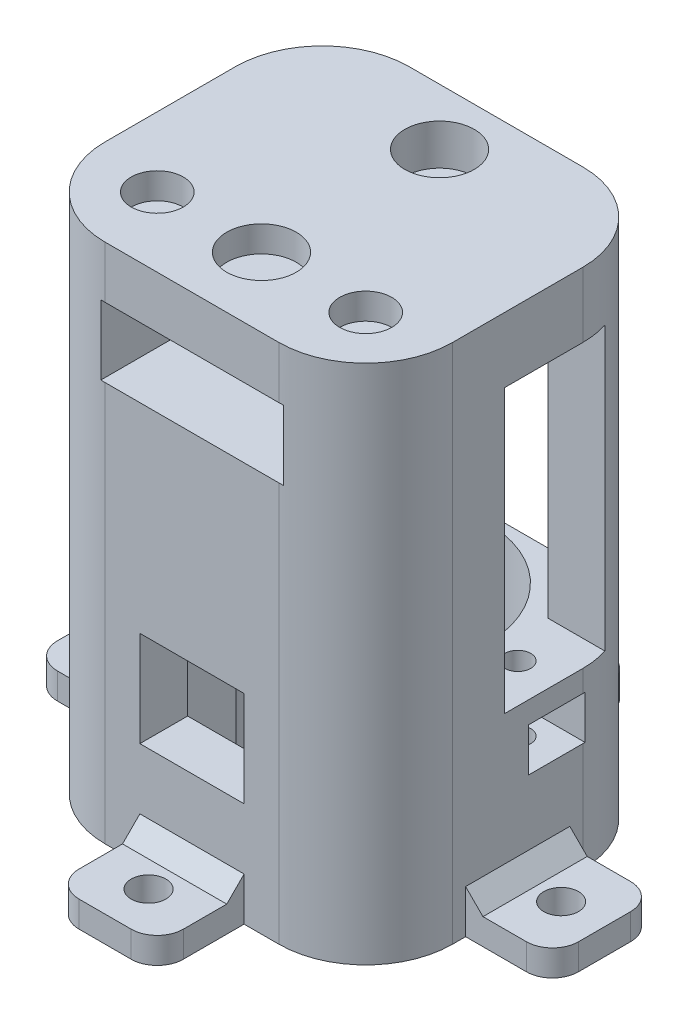
SolidWorks part; units mm, degrees
ref_plane "Plano frontal" through (0, 0, 0) normal (0, 0, 1) x (1, 0, 0)
ref_plane "Plano superior" through (0, 0, 0) normal (0, 1, 0) x (1, 0, 0)
ref_plane "Plano direito" through (0, 0, 0) normal (1, 0, 0) x (0, 0, -1)
sketch "Esboço2" plane through (0, 0, 0) normal (0, 1, 0) x (1, 0, 0)
  line L1 (0, 0) -> (40, 0)
  line L2 (0, 0) -> (0, 35)
  line L3 (0, 35) -> (40, 35)
  line L4 (40, 0) -> (40, 35)
  dimension "D1" = 40
  dimension "D2" = 35
extrude "Base" add sketch "Esboço2" along normal blind 20
sketch "Esboço3" plane through (0, 20, 0) normal (0, 1, 0) x (1, 0, 0)
  line L0 (20, -2.1425) -> (20, 46.202) construction
  line L1 (-2.8555, 22) -> (47.4642, 22) construction
  line L2 (40, 0) -> (40, 35) construction
  line L3 (40, 35) -> (0, 35) construction
  line L5 (11.25, 5.5) -> (28.75, 5.5)
  line L6 (11.25, 5.5) -> (11.25, 14.5)
  line L7 (11.25, 14.5) -> (28.75, 14.5)
  line L8 (28.75, 5.5) -> (28.75, 14.5)
  line L9 (11.25, 5.5) -> (28.75, 14.5) construction
  line L10 (11.25, 14.5) -> (28.75, 5.5) construction
  circle A0 centre (20, 22) radius 12
  point P10 (20, 10)
  dimension "D1" = 24
  dimension "D2" = 20
  dimension "D3" = 13
  dimension "D4" = 17.5
  dimension "D5" = 9
  dimension "D6" = 16.5
extrude "Furo do encaixe do motor" cut sketch "Esboço3" against normal through all contours A0 L7 L6 L5 L8 | L7 A0 | L7 A0 region at (20, 20, -8.4409) region at (20, 20, -23.3816) region at (20, 20, -12.6552)
sketch "Esboço5" plane through (0, 20, 0) normal (0, 1, 0) x (1, 0, 0)
  line L0 (41.6655, 22) -> (-3.8205, 22) construction
  line L1 (20, 37.517) -> (20, 6.483) construction
  circle A0 centre (4.5, 22) radius 1.5
  circle A1 centre (35.5, 22) radius 1.5
  point P10 (20, 22)
  dimension "D1" = 3
  dimension "D2" = 3
  dimension "D3" = 15.5
  dimension "D4" = 15.5
extrude "Furo dos parafusos do motor" cut sketch "Esboço5" against normal through all
sketch "Esboço6" plane through (40, 0, 0) normal (1, 0, 0) x (0, 0, -1)
  line L0 (22, 21.0896) -> (22, -1.5414) construction
  line L1 (35, 20) -> (35, 0) construction
  line L2 (0, 20) -> (35, 20) construction
  line L3 (18.75, 17.5) -> (25.25, 17.5)
  line L4 (18.75, 17.5) -> (18.75, 12.5)
  line L5 (18.75, 12.5) -> (25.25, 12.5)
  line L6 (25.25, 17.5) -> (25.25, 12.5)
  line L7 (18.75, 17.5) -> (25.25, 12.5) construction
  line L8 (18.75, 12.5) -> (25.25, 17.5) construction
  point P4 (22, 15)
  dimension "D1" = 13
  dimension "D2" = 6.5
  dimension "D3" = 5
  dimension "D4" = 5
extrude "Furo da arruela para parafusos do motor" cut sketch "Esboço6" against normal through all
sketch "Esboço7" plane through (0, 20, 0) normal (0, 1, 0) x (1, 0, 0)
  line L0 (20, 16.9507) -> (20, -1.8604) construction
  line L1 (40, 0) -> (40, 35) construction
  line L3 (14, -3.2615) -> (26, -3.2615)
  line L4 (14, -3.2615) -> (14, 18.3519)
  line L5 (14, 18.3519) -> (26, 18.3519)
  line L6 (26, -3.2615) -> (26, 18.3519)
  line L7 (14, -3.2615) -> (26, 18.3519) construction
  line L8 (14, 18.3519) -> (26, -3.2615) construction
  point P4 (20, 7.5452)
  dimension "D1" = 20
  dimension "D2" = 12
extrude "Calha para os cabos do motor" cut sketch "Esboço7" against normal blind 8
sketch "Esboço10" plane through (0, 20, 0) normal (0, 1, 0) x (1, 0, 0)
  line L0 (40, 0) -> (40, 35) construction
  line L1 (0, 35) -> (7, 35)
  line L2 (0, 35) -> (0, 28)
  line L3 (0, 28) -> (7, 28)
  line L4 (7, 35) -> (7, 28)
  line L5 (40, 35) -> (33, 35)
  line L6 (40, 35) -> (40, 28)
  line L7 (40, 28) -> (33, 28)
  line L8 (33, 35) -> (33, 28)
  line L9 (0, 0) -> (40, 0)
  line L10 (0, 0) -> (0, 5.5)
  line L11 (0, 5.5) -> (40, 5.5)
  line L12 (40, 0) -> (40, 5.5)
  line L14 (0, 5.5) -> (7, 5.5)
  line L15 (0, 5.5) -> (0, 16)
  line L16 (0, 16) -> (7, 16)
  line L17 (7, 5.5) -> (7, 16)
  line L18 (40, 5.5) -> (33, 5.5)
  line L19 (40, 5.5) -> (40, 16)
  line L20 (40, 16) -> (33, 16)
  line L21 (33, 5.5) -> (33, 16)
  line M13 (28.75, 5.5) -> (26, 5.5)
  line M14 (26, 5.5) -> (26, 0)
  line M15 (26, 0) -> (40, 0)
  line M16 (40, 0) -> (40, 35)
  line M17 (40, 35) -> (0, 35)
  line M18 (0, 35) -> (0, 0)
  line M19 (0, 0) -> (14, 0)
  line M20 (14, 0) -> (14, 5.5)
  line M21 (14, 5.5) -> (11.25, 5.5)
  dimension "D1" = 5.5
  dimension "D2" = 7
  dimension "D3" = 7
  dimension "D4" = 7
  dimension "D5" = 7
  dimension "D6" = 7
  dimension "D7" = 7
  dimension "D8" = 10.5
  dimension "D9" = 10.5
extrude "Base extendida" add sketch "Esboço10" along normal blind 35 contours L11 L17 L16 M18 | L11 M18 M19 M20 M21 | L11 M13 M14 M15 M16 | L11 L9 M20 M14 | L21 L11 L20 M16 | L8 L7 M17 M16 | L4 L3 M17 M18 region at (3.5, 20, -31.5) region at (36.5, 20, -31.5) region at (3.5, 20, -10.75) region at (7, 20, -2.75) region at (36.5, 20, -10.75) region at (20, 20, -2.75) region at (33, 20, -2.75)
sketch "Esboço11" plane through (7, 0, 0) normal (1, 0, 0) x (0, 0, -1)
  line L0 (16, 55) -> (16, 45)
  line L1 (16, 55) -> (16, 20) construction
  line L2 (16, 55) -> (5.5, 55)
  line L3 (5.5, 55) -> (16, 55) construction
  line L4 (5.5, 55) -> (5.5, 30.0044)
  line L5 (16, 45) -> (5.5, 30.0044)
  dimension "D1" = 10.5
  dimension "D2" = 35
  dimension "D3" = 10
extrude "Chanfro da base extendida" add sketch "Esboço11" along normal through all
sketch "Esboço12" plane through (0, 0, -16) normal (0, 0, -1) x (-1, 0, 0)
  line L1 (-40, 55) -> (-33, 55)
  line L2 (-40, 55) -> (-40, 52.5)
  line L3 (-40, 52.5) -> (-33, 52.5)
  line L4 (-33, 55) -> (-33, 52.5)
  dimension "D1" = 2.5
  dimension "D2" = 7
extrude "Ponte 1" add sketch "Esboço12" along normal through all
sketch "Esboço13" plane through (0, 0, -16) normal (0, 0, -1) x (-1, 0, 0)
  line L1 (0, 55) -> (-7, 55)
  line L2 (0, 55) -> (0, 52.5)
  line L3 (0, 52.5) -> (-7, 52.5)
  line L4 (-7, 55) -> (-7, 52.5)
  dimension "D1" = 2.5
  dimension "D2" = 7
extrude "Ponte 2" add sketch "Esboço13" along normal through all
sketch "Esboço14" plane through (0, 55, 0) normal (0, 1, 0) x (1, 0, 0)
  line L1 (0, 0) -> (40, 0)
  line L2 (0, 0) -> (0, 35)
  line L3 (0, 35) -> (40, 35)
  line L4 (40, 0) -> (40, 35)
extrude "Telhado" add sketch "Esboço14" along normal blind 5
sketch "Esboço18" plane through (0, 60, 0) normal (0, 1, 0) x (1, 0, 0)
  line L0 (20, 37.438) -> (20, -2.8891) construction
  line L1 (40, 0) -> (40, 35) construction
  line L2 (40, 35) -> (0, 35) construction
  circle A0 centre (20, 28.5) radius 4
  dimension "D2" = 8
  dimension "D3" = 6.5
  dimension "D1" = 20
extrude "Furo do Eixo" cut sketch "Esboço18" against normal blind 8
sketch "Esboço20" plane through (0, 0, -5.5) normal (0, 0, -1) x (-1, 0, 0)
  line L0 (-33, 20) -> (-7, 20) construction
  line L1 (-26, 17) -> (-14, 17)
  line L2 (-26, 17) -> (-26, 23)
  line L3 (-26, 23) -> (-14, 23)
  line L4 (-14, 17) -> (-14, 23)
  line L5 (-26, 17) -> (-14, 23) construction
  line L6 (-26, 23) -> (-14, 17) construction
  point P0 (-20, 20)
  dimension "D1" = 12
  dimension "D2" = 6
extrude "Calha para os cabos do motor superior" cut sketch "Esboço20" against normal blind 15
sketch "Esboço21" plane through (0, 17.5, 0) normal (0, -1, 0) x (1, 0, 0)
  circle A0 centre (35.5, -22) radius 1.5
extrude "Cama furo do parafuso 1" add sketch "Esboço21" against normal blind 0.3
sketch "Esboço22" plane through (0, 17.5, 0) normal (0, -1, 0) x (1, 0, 0)
  circle A0 centre (4.5, -22) radius 1.5
extrude "Cama furo do parafuso 2" add sketch "Esboço22" against normal blind 0.3
sketch "Esboço23" plane through (0, 55, 0) normal (0, -1, 0) x (1, 0, 0)
  line L0 (33, -30.4716) -> (22.9081, -16)
  line L1 (7, -30.4716) -> (17.2307, -16)
  line L2 (33, -16) -> (33, -30.4716)
  line L3 (33, -35) -> (33, -16) construction
  line L4 (7, -16) -> (33, -16) construction
  line L5 (22.9081, -16) -> (33, -16)
  line L6 (17.2307, -16) -> (7, -16)
  line L7 (7, -35) -> (7, -16) construction
  line L8 (7, -30.4716) -> (7, -16)
  line M3 (33, -35) -> (33, -16)
  line M4 (33, -16) -> (7, -16)
  line M5 (7, -16) -> (7, -35)
extrude "Cama para o telhado" add sketch "Esboço23" along normal blind 0.4 contours M4 M3 | M4 M5 region at (10.4102, 55, -20.8239) region at (29.636, 55, -20.8239)
sketch "Esboço24" plane through (0, 55, 0) normal (0, -1, 0) x (1, 0, 0)
  circle A0 centre (20, -28.5) radius 4
extrude "Cama para o furo do eixo" add sketch "Esboço24" against normal blind 0.3
fillet "Filete1" radius 10 1 edges at (40, 30, -35) type face fillet first side face at (40, 30, -17.5) second side face at (20, 37.5, -35)
fillet "Filete2" radius 10 1 edges at (0, 30, -35) type face fillet first side face at (0, 36.25, -22) second side face at (16.75, 33.75, -35)
fillet "Filete3" radius 10 1 edges at (0, 30, 0) type face fillet first side face at (0, 27.0833, -18.2917) second side face at (20, 17.5, 0)
fillet "Filete4" radius 10 1 edges at (40, 30, 0) type face fillet first side face at (40, 27.0833, -18.2917) second side face at (20, 17.5, 0)
sketch "Esboço26" plane through (0, 0, 0) normal (0, 0, 1) x (1, 0, 0)
  line L0 (20, 62.2763) -> (20, -5.3749) construction
  line L1 (40, 60) -> (40, 0) construction
  line L2 (10, 60) -> (30, 60) construction
  line L3 (9.5, 54) -> (30.5, 54)
  line L4 (9.5, 54) -> (9.5, 46)
  line L5 (9.5, 46) -> (30.5, 46)
  line L6 (30.5, 54) -> (30.5, 46)
  line L7 (9.5, 54) -> (30.5, 46) construction
  line L8 (9.5, 46) -> (30.5, 54) construction
  point P5 (20, 50)
  dimension "D1" = 20
  dimension "D2" = 21
  dimension "D3" = 8
  dimension "D4" = 6
extrude "Corte-extrusão1" cut sketch "Esboço26" against normal blind 20
sketch "Esboço28" plane through (40, 0, 0) normal (1, 0, 0) x (0, 0, -1)
  line L0 (17.5, -2.6941) -> (17.5, 10.6017) construction
  line L1 (10, 0) -> (25, 0) construction
  line L2 (11.5, 0) -> (23.5, 0)
  line L3 (11.5, 0) -> (11.5, 3)
  line L4 (11.5, 3) -> (23.5, 3)
  line L5 (23.5, 0) -> (23.5, 3)
  dimension "D1" = 17.5
  dimension "D2" = 12
  dimension "D3" = 3
  dimension "D4" = 6
extrude "Ressalto-extrusão11" add sketch "Esboço28" along normal blind 10
sketch "Esboço29" plane through (0, 3, 0) normal (0, 1, 0) x (1, 0, 0)
  line L0 (40, 23.5) -> (40, 11.5) construction
  line L1 (50, 11.5) -> (40, 11.5) construction
  circle A0 centre (45, 17.5) radius 2
  point P4 (40, 17.5)
  dimension "D1" = 4
  dimension "D2" = 5
  dimension "D3" = 6
extrude "Corte-extrusão2" cut sketch "Esboço29" against normal blind 10
ref_plane "Plano1" through (20, 0, 0) normal (1, 0, 0) x (0, 0, -1)
mirror "Espelhar1" about plane through (20, 0, 0) normal (1, 0, 0) of "Ressalto-extrusão11"
mirror "Espelhar2" about plane through (20, 0, 0) normal (1, 0, 0) of "Corte-extrusão2"
sketch "Esboço30" plane through (0, 0, 0) normal (0, 0, 1) x (1, 0, 0)
  line L0 (20, -2.5658) -> (20, 6.588) construction
  line L1 (10, 0) -> (30, 0) construction
  line L2 (14, 0) -> (26, 0)
  line L3 (14, 0) -> (14, 3)
  line L4 (14, 3) -> (26, 3)
  line L5 (26, 0) -> (26, 3)
  dimension "D1" = 20
  dimension "D2" = 3
  dimension "D3" = 12
  dimension "D4" = 6
extrude "Ressalto-extrusão12" add sketch "Esboço30" along normal blind 10
sketch "Esboço31" plane through (0, 3, 0) normal (0, 1, 0) x (1, 0, 0)
  line L0 (26, 0) -> (14, 0) construction
  line L1 (26, -10) -> (26, 0) construction
  circle A0 centre (20, -5) radius 2
  dimension "D1" = 4
  dimension "D2" = 5
  dimension "D3" = 6
extrude "Corte-extrusão3" cut sketch "Esboço31" against normal blind 10
chamfer "Chanfro1" distance 2 angle 45 1 edges at (40, 3, -17.5)
chamfer "Chanfro2" distance 2 angle 45 1 edges at (0, 3, -17.5)
chamfer "Chanfro3" distance 2 angle 45 1 edges at (20, 3, 0)
fillet "Filete5" radius 3 1 edges at (50, 1.5, -11.5) type face fillet first side face at (44.4, 2.2, -11.5) second side face at (50, 1.5, -17.5)
fillet "Filete6" radius 3 1 edges at (50, 1.5, -23.5) type face fillet first side face at (44.4, 2.2, -23.5) second side face at (50, 1.5, -19)
fillet "Filete7" radius 3 1 edges at (26, 1.5, 10) type face fillet first side face at (20, 1.5, 10) second side face at (26, 2.2, 4.4)
fillet "Filete8" radius 3 1 edges at (14, 1.5, 10) type face fillet first side face at (14, 2.2, 4.4) second side face at (18.5, 1.5, 10)
fillet "Filete9" radius 3 1 edges at (-10, 1.5, -11.5) type face fillet first side face at (-4.4, 2.2, -11.5) second side face at (-10, 1.5, -17.5)
fillet "Filete10" radius 3 1 edges at (-10, 1.5, -23.5) type face fillet first side face at (-4.4, 2.2, -23.5) second side face at (-10, 1.5, -19)
ref_plane "Plano3" through (0, 0, -17.5) normal (0, 0, 1) x (1, 0, 0)
mirror "Espelhar5" about plane through (0, 0, -17.5) normal (0, 0, 1) of "Filete8", "Filete7", "Corte-extrusão3", "Ressalto-extrusão12"
chamfer "Chanfro4" distance 2 angle 45 1 edges at (20, 3, -35)
sketch "Esboço32" plane through (0, 60, 0) normal (0, 1, 0) x (1, 0, 0)
  line L0 (20, 46.9683) -> (20, -12.9151) construction
  line L1 (45.7569, 8) -> (-12.8125, 8) construction
  circle A0 centre (20, 8) radius 4
  circle A1 centre (8, 8) radius 3
  circle A2 centre (32, 8) radius 3
  dimension "D2" = 8
  dimension "D3" = 8
  dimension "D4" = 6
  dimension "D5" = 6
  dimension "D6" = 12
  dimension "D7" = 12
  dimension "D1" = 20
extrude "Corte-extrusão4" cut sketch "Esboço32" against normal blind 3
